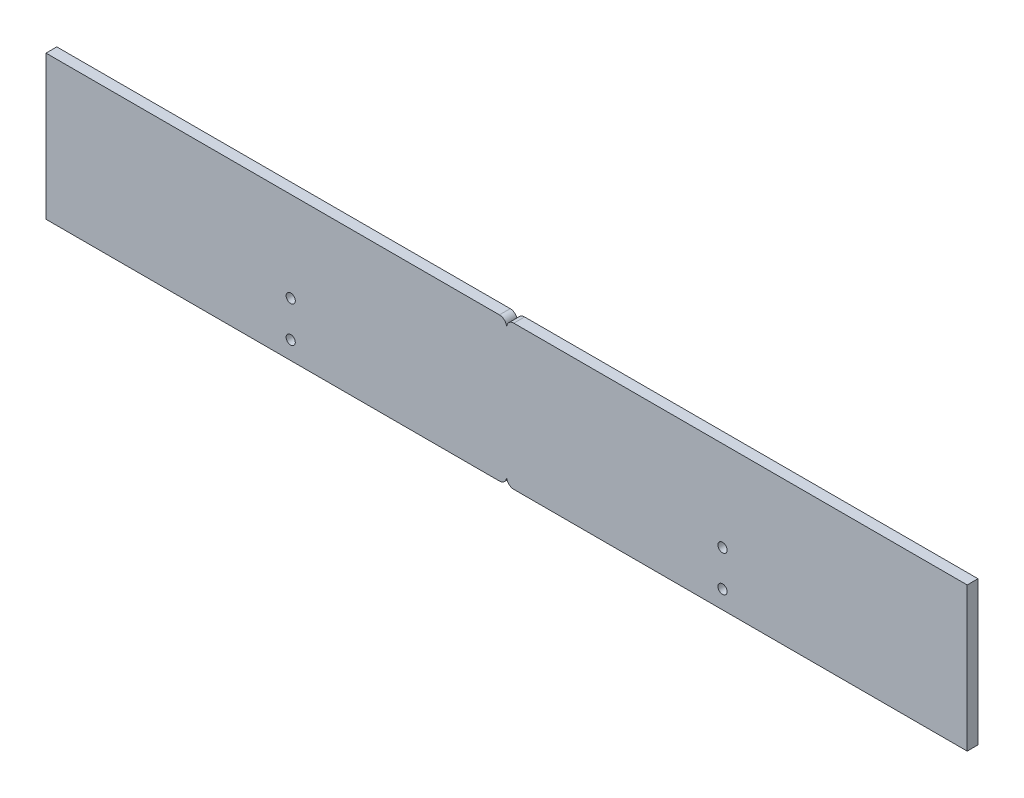
SolidWorks part; units mm, degrees
material "Клен"
ref_plane "Спереди" through (0, 0, 0) normal (0, 0, 1) x (1, 0, 0)
ref_plane "Сверху" through (0, 0, 0) normal (0, 1, 0) x (1, 0, 0)
ref_plane "Справа" through (0, 0, 0) normal (1, 0, 0) x (0, 0, -1)
sketch "Эскиз1" plane through (0, 0, 0) normal (0, 0, 1) x (1, 0, 0)
  line L0 (0, -164.4615) -> (512, -244.4615) construction
  line L1 (0, -244.4615) -> (512, -244.4615)
  line L2 (0, -244.4615) -> (0, -164.4615)
  line L3 (0, -164.4615) -> (512, -164.4615)
  line L4 (512, -244.4615) -> (512, -164.4615)
  line L5 (512, -164.4615) -> (0, -244.4615) construction
  line L6 (256, -229.8055) -> (256, -159.0937) construction
extrude "Бобышка-Вытянуть1" add sketch "Эскиз1" along normal blind 6 contours L3 L4 L1 L2
sketch "Эскиз2" plane through (0, 0, 6) normal (0, 0, 1) x (1, 0, 0)
  line L0 (0, -244.4615) -> (512, -164.4615) construction
  line L1 (512, -164.4615) -> (512, -244.4615) construction
  line L2 (512, -244.4615) -> (0, -164.4615) construction
  line L4 (256, -159.5243) -> (256, -268.7219) construction
  line L5 (259.9873, -244.4615) -> (252.0127, -244.4615)
  line L8 (0, -244.4615) -> (0, -164.4615) construction
  line L12 (0, -204.4615) -> (512, -204.4615) construction
  line L13 (0, -164.4615) -> (512, -164.4615) construction
  line L14 (0, -244.4615) -> (512, -244.4615) construction
  line L15 (259.9873, -164.4615) -> (252.0127, -164.4615)
  arc A0 (252.0127, -164.4615) -> (256, -168.4488) centre (252.0127, -168.4488) cw
  arc A1 (259.9873, -164.4615) -> (256, -168.4488) centre (259.9873, -168.4488) ccw
  arc A2 (259.9873, -244.4615) -> (256, -240.4743) centre (259.9873, -240.4743) cw
  arc A3 (252.0127, -244.4615) -> (256, -240.4743) centre (252.0127, -240.4743) ccw
  circle A4 centre (376, -234.4615) radius 2.55
  circle A5 centre (376, -214.4615) radius 2.55
  circle A6 centre (136, -234.4615) radius 2.55
  circle A7 centre (136, -214.4615) radius 2.55
  point P10 (256, -164.4615)
  point P11 (256, -244.4615)
  point P14 (0, -204.4615)
  point P16 (512, -204.4615)
  point P22 (256, -204.4615)
  point P29 (256, -164.4615)
extrude "Вырез-Вытянуть1" cut sketch "Эскиз2" against normal through all
